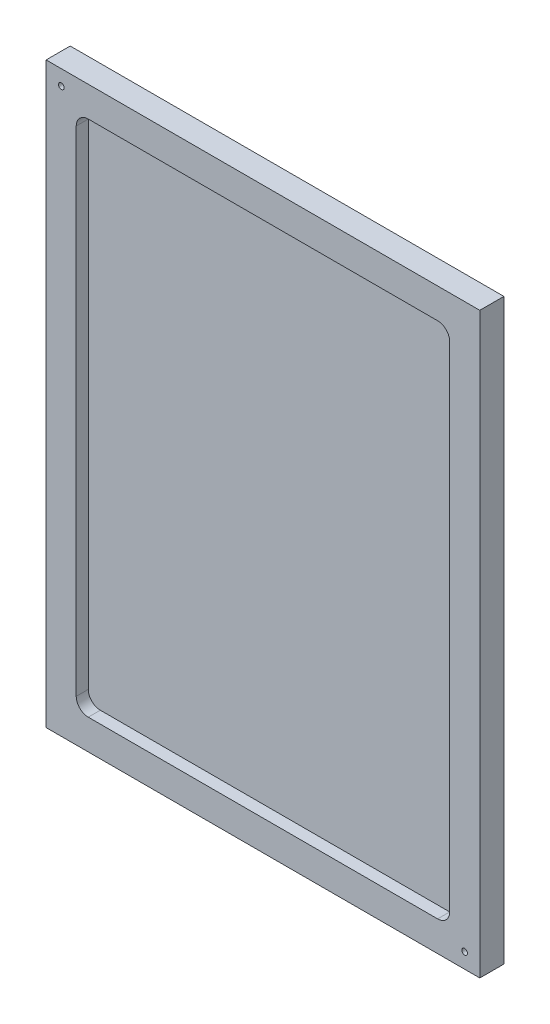
SolidWorks part; units mm, degrees
ref_plane "Front Plane" through (0, 0, 0) normal (0, 0, 1) x (1, 0, 0)
ref_plane "Top Plane" through (0, 0, 0) normal (0, 1, 0) x (1, 0, 0)
ref_plane "Right Plane" through (0, 0, 0) normal (1, 0, 0) x (0, 0, -1)
sketch "Sketch1" plane through (0, 0, 0) normal (0, 0, 1) x (1, 0, 0)
  line L1 (114.3, -152.4) -> (-114.3, -152.4)
  line L2 (114.3, -152.4) -> (114.3, 152.4)
  line L3 (114.3, 152.4) -> (-114.3, 152.4)
  line L4 (-114.3, -152.4) -> (-114.3, 152.4)
  line L5 (114.3, -152.4) -> (-114.3, 152.4) construction
  line L6 (114.3, 152.4) -> (-114.3, -152.4) construction
  point P0 (0, 0)
  dimension "D1" = 228.6
  dimension "D2" = 304.8
extrude "Boss-Extrude1" add sketch "Sketch1" along normal blind 12.7
sketch "Sketch2" plane through (0, 0, 12.7) normal (0, 0, 1) x (1, 0, 0)
  line L0 (-114.3, 152.4) -> (-114.3, -152.4) construction
  line L1 (92.075, -136.525) -> (-92.075, -136.525)
  line L2 (98.425, -130.175) -> (98.425, 130.175)
  line L3 (92.075, 136.525) -> (-92.075, 136.525)
  line L4 (-98.425, -130.175) -> (-98.425, 130.175)
  line L5 (98.425, -136.525) -> (-98.425, 136.525) construction
  line L6 (98.425, 136.525) -> (-98.425, -136.525) construction
  line L7 (114.3, 152.4) -> (-114.3, 152.4) construction
  arc A0 (-92.075, -136.525) -> (-98.425, -130.175) centre (-92.075, -130.175) cw
  arc A1 (92.075, -136.525) -> (98.425, -130.175) centre (92.075, -130.175) ccw
  arc A2 (98.425, 130.175) -> (92.075, 136.525) centre (92.075, 130.175) ccw
  arc A3 (-92.075, 136.525) -> (-98.425, 130.175) centre (-92.075, 130.175) ccw
  point P0 (0, 0)
  dimension "D3" = 6.35
  dimension "D1" = 15.875
  dimension "D2" = 15.875
extrude "Cut-Extrude1" cut sketch "Sketch2" against normal blind 6.35
hole_wizard "Ø3.0 (3) Diameter Hole1" positions "Sketch3" profile "Sketch4" hole size "Ø3.0" standard "ANSI Metric"
sketch "Sketch3" plane through (0, 0, 12.7) normal (0, 0, 1) x (1, 0, 0)
  line L0 (-114.3, -152.4) -> (114.3, -152.4) construction
  line L1 (114.3, -152.4) -> (114.3, 152.4) construction
  line L2 (-114.3, 152.4) -> (-114.3, -152.4) construction
  line L4 (114.3, 152.4) -> (-114.3, 152.4) construction
  point P0 (-106.3, 144.4)
  point P2 (106.3, -144.4)
  point P15 (-98.2127, 152.4)
  point P18 (0, 0)
  dimension "D1" = 8
  dimension "D2" = 8
  dimension "D3" = 8
  dimension "D4" = 8
sketch "Sketch4" plane through (-106.3, 144.4, 12.7) normal (1, 0, 0) x (0, -1, 0)
  line L0 (0, 0) -> (0, 5.9013)
  line L1 (0, 5.9013) -> (1.5, 5)
  line L2 (1.5, 5) -> (1.5, 0)
  line L5 (1.5, 0) -> (0, 0)
  line L10 (0, 5.9013) -> (-1.5, 5) construction
  line L11 (0, -6.35) -> (0, 107.95) construction
  dimension "Hole Dia." = 3
  dimension "Hole Depth" = 5
  dimension "Drill Angle" = 118
